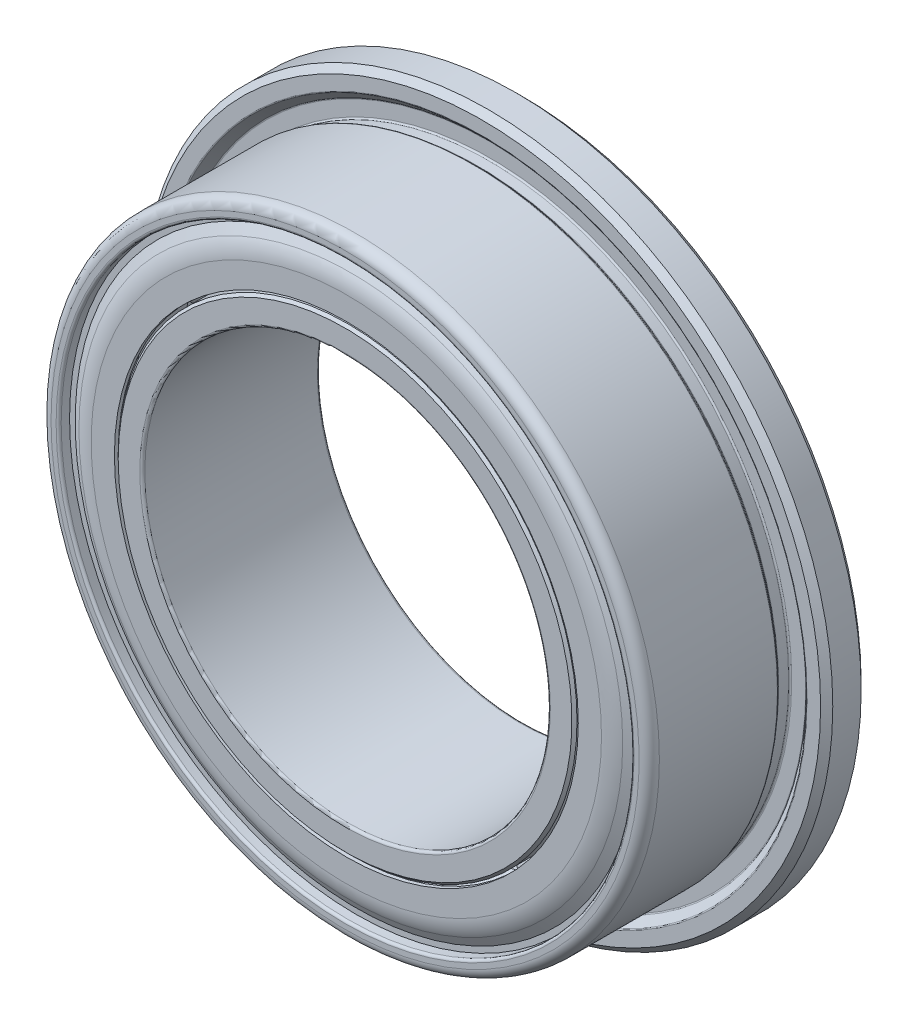
SolidWorks part; units mm, degrees
note: '?' marks a value the reader was unsure of.
ref_plane "Front Plane" through (0, 0, 0) normal (0, 0, 1) x (1, 0, 0)
ref_plane "Top Plane" through (0, 0, 0) normal (0, 1, 0) x (1, 0, 0)
ref_plane "Right Plane" through (0, 0, 0) normal (1, 0, 0) x (0, 0, -1)
sketch "Sketch1" plane through (0, 0, 0) normal (1, 0, 0) x (0, 0, -1)
  line L0 (-1.75, 0) -> (1.75, 0) construction
  line L1 (0, 6) -> (0, -6) construction
  line L2 (1.75, 6) -> (-1.75, 6)
  line L4 (-1.75, 6) -> (-1.75, 5.65)
  line L5 (-1.75, 5.65) -> (-0.645, 5.65)
  line L6 (1.75, 5.65) -> (0.645, 5.65)
  line L7 (1.75, 6) -> (1.75, 5.65)
  line L9 (0, 6) -> (0, 5) construction
  line L10 (0, 5) -> (0, 4) construction
  line L11 (-1.75, -5.65) -> (-1.75, 5.65) construction
  line L12 (0.95, -6.8) -> (1.75, -6.8)
  line L13 (0.95, -6.8) -> (0.95, 6.8)
  line L14 (0.95, 6.8) -> (1.75, 6.8)
  line L15 (1.75, -6.8) -> (1.75, 6.8)
  line L16 (0.95, -6.8) -> (1.75, 6.8) construction
  line L17 (0.95, 6.8) -> (1.75, -6.8) construction
  line L18 (-1.75, -4.525) -> (-1.75, 4.525)
  line L24 (0, -6) -> (-1.75, -6)
  line L25 (0, 4) -> (0, 6) construction
  line L26 (-1.75, 4.525) -> (-1.75, 4)
  line L27 (-1.75, 4) -> (1.75, 4)
  line L28 (1.75, 4) -> (1.75, 4.525)
  line L29 (1.75, 4.525) -> (0.445, 4.525)
  line L30 (-1.75, 4.525) -> (-0.445, 4.525)
  line L31 (-0.645, 5.65) -> (-0.645, 5.425)
  line L32 (-0.645, 5.425) -> (-0.445, 5.425)
  line L33 (0.645, 5.65) -> (0.645, 5.425)
  line L34 (0.645, 5.425) -> (0.445, 5.425)
  arc A3 (-0.445, 4.525) -> (0.445, 4.525) centre (0, 5) ccw
  circle A5 centre (0, 4.9791) radius 0.6
  arc A6 (-0.445, 5.425) -> (0.445, 5.425) centre (0, 4.9791) cw
  point P7 (-1.75, 5.65)
  point P13 (-1.65, 5.65)
  point P14 (0, 4)
  point P15 (1.35, 0)
  point P22 (1.75, 0)
  point P25 (-1.75, 0)
  point P27 (-1.75, 0)
  point P28 (-1.55, 5.65)
  point P29 (-1.45, 5.65)
  point P30 (-1.35, 5.65)
  point P31 (-1.25, 5.65)
  point P32 (-1.15, 5.65)
  point P33 (-1.05, 5.65)
  point P34 (-0.95, 5.65)
  point P37 (-0.85, 5.65)
  point P45 (-0.75, 5.65)
  point P46 (0, 5.6091)
  point P47 (-0.65, 5.65)
  point P50 (0, 4.3491)
  point P51 (0, 4.3791)
  point P52 (0, 5.5791)
  dimension "D3" = 1.2
  dimension "Shaft Dia" = 8
  dimension "Flange Thickness" = 0.8
  dimension "Flange OD" = 13.6
  dimension "D11" = 11.3
  dimension "D10" = 9.05
  dimension "Width" = 3.5
  dimension "OD" = 12
  dimension "D4" = 0.03
  dimension "D5" = 0.2
  dimension "D6" = 0.1
  dimension "D7" = 0.9
  dimension "D1" = 12
sketch "Sketch2" plane through (0, 0, 0) normal (0, 0, 1) x (1, 0, 0)
  line L0 (0, -4.525) -> (0, 4.525) construction
  circle A0 centre (0, 0) radius 4
  dimension "D1" = 8
sketch "Sketch3" plane through (0, 0, 0) normal (1, 0, 0) x (0, 0, -1)
  line L2 (-1.75, 6) -> (-1.75, 5.65) construction
  line L3 (1.75, 6) -> (-1.75, 6) construction
  line L4 (1.75, 6) -> (1.75, 5.65) construction
  line L5 (1.75, 5.65) -> (0.645, 5.65) construction
  line L6 (-1.75, 5.65) -> (-0.645, 5.65) construction
  line L13 (-1.75, 6) -> (-1.75, 5.65)
  line L21 (1.75, 6) -> (-1.75, 6)
  line L22 (1.75, 6) -> (1.75, 5.65)
  line L23 (1.75, 5.65) -> (0.645, 5.65)
  line L24 (-1.75, 5.65) -> (-0.645, 5.65)
  line L25 (1.75, 4) -> (-1.75, 4)
  line L27 (-1.75, 4) -> (-1.75, 4.525)
  line L28 (-1.75, 4.525) -> (-0.445, 4.525)
  line L29 (0.645, 5.65) -> (0.645, 5.425) construction
  line L30 (1.75, 4) -> (1.75, 4.525)
  line L31 (1.75, -6.8) -> (1.75, 6.8) construction
  line L32 (1.75, 4.525) -> (0.445, 4.525)
  line L33 (0.645, 5.425) -> (0.445, 5.425) construction
  line L34 (-0.645, 5.425) -> (-0.445, 5.425) construction
  line L35 (-0.645, 5.65) -> (-0.645, 5.425) construction
  line L36 (0.645, 5.65) -> (0.645, 5.425)
  line L37 (0.645, 5.425) -> (0.445, 5.425)
  line L38 (-0.645, 5.425) -> (-0.445, 5.425)
  line L39 (-0.645, 5.65) -> (-0.645, 5.425)
  arc A4 (0.445, 5.425) -> (-0.445, 5.425) centre (0, 4.9791) ccw construction
  arc A5 (-0.445, 4.525) -> (0.445, 4.525) centre (0, 5) ccw construction
  arc A6 (-0.445, 4.525) -> (0.445, 4.525) centre (0, 5) ccw
  arc A7 (0.445, 5.425) -> (-0.445, 5.425) centre (0, 4.9791) ccw
  point P15 (0, 4)
revolve "Revolve1" add sketch "Sketch3" angle 360 about L0
sketch "Sketch5" plane through (0, 0, 0) normal (1, 0, 0) x (0, 0, -1)
  line L0 (-0.6, 4.9791) -> (0.6, 4.9791)
  line L1 (0, 6) -> (0, -6) construction
  circle A0 centre (0, 4.9791) radius 0.6 construction
  arc A1 (-0.6, 4.9791) -> (0.6, 4.9791) centre (0, 4.9791) cw
revolve "Revolve3" add sketch "Sketch5" angle 360 about L0
ref_axis "Axis1" through (0, 0, -1.75) along (0, 0, 1)?
pattern_circular "CirPattern1" count 12 over 360 about axis through (0, 0, 0) along (0, 0, 1) of bodies 122
sketch "Sketch6" plane through (0, 0, 0) normal (1, 0, 0) x (0, 0, -1)
  line L1 (-1.725, 4.525) -> (-1.725, 5.0332)
  line L2 (-1.6366, 5.3632) -> (-1.5345, 5.54)
  line L4 (-1.5345, 5.54) -> (-1.4479, 5.54) construction
  line L5 (-1.5345, 5.54) -> (-1.5345, 5.65)
  line L6 (-1.5345, 5.65) -> (-1.4479, 5.65)
  line L7 (-1.4479, 5.54) -> (-1.65, 5.1899)
  line L8 (-1.65, 5.1899) -> (-1.65, 4.525)
  line L9 (-1.65, 4.525) -> (-1.725, 4.525)
  line L10 (0, 6) -> (0, -6) construction
  line L11 (-1.4479, 5.65) -> (-1.4479, 5.54)
  line L12 (-1.75, 5.65) -> (-0.645, 5.65) construction
  line L14 (0, 6) -> (0, 5.6091) construction
  arc A0 (-1.725, 5.0332) -> (-1.6366, 5.3632) centre (-1.065, 5.0332) cw
  point P22 (-1.725, 5.21)
  dimension "D8" = 0.66
  dimension "D1" = 30
  dimension "D3" = 0.075
  dimension "D6" = 0.33
  dimension "D5" = 1.125
  dimension "D7" = 0.11
revolve "Revolve4" add sketch "Sketch6" angle 360 about L0
mirror "Mirror1" about plane through (0, 0, 0) normal (0, 0, 1) of bodies 138
sketch "Sketch9" plane through (0, 0, 1.725) normal (0, 0, 1) x (1, 0, 0)
  circle A2 centre (0, 0) radius 4.575
  circle A3 centre (0, 0) radius 4.575
  dimension "D1" = 0.05
extrude "Cut-Extrude1" cut sketch "Sketch9" against normal through all
sketch "Sketch7" plane through (0, 0, 0) normal (1, 0, 0) x (0, 0, -1)
  line L0 (1.75, 0) -> (-1.75, 0) construction
  line L2 (0.95, 6.8) -> (1.75, 6.8)
  line L3 (0.95, 6.8) -> (0.95, 5.65)
  line L4 (0.95, 5.65) -> (1.75, 5.65)
  line L5 (1.75, 6.8) -> (1.75, 5.65)
revolve "Revolve5" add sketch "Sketch7" angle 360 about L0
fillet "Fillet2" radius 0.2 1 edges at (6, 0, 1.75)
fillet "Fillet3" radius 0.05 4 edges at (5.65, 0, -1.75) (5.65, 0, 1.75) (5.65, 0, -0.645) (5.65, 0, 0.645)
fillet "Fillet6" radius 0.05 4 edges at (4.525, 0, -1.75) (4.525, 0, -0.445) (4.525, 0, 0.445) (4.525, 0, 1.75)
sketch "Sketch8" plane through (0, 0, 0) normal (1, 0, 0) x (0, 0, -1)
  line L7 (0.95, 6.8) -> (0.95, 6) construction
  line L8 (0.95, 6.4) -> (1.11, 6.24)
  line L9 (1.11, 6.24) -> (1.11, 5.92)
  line L10 (1.11, 5.92) -> (0.87, 5.92)
  line L11 (0.87, 5.92) -> (0.79, 6)
  line L12 (0.95, 6) -> (-1.55, 6) construction
  line L13 (0.79, 6) -> (0.95, 6)
  line L14 (0.95, 6) -> (0.95, 6.4)
  dimension "D1" = 45
  dimension "D2" = 45
  dimension "D3" = 0.16
  dimension "D5" = 0.08
revolve "Cut-Revolve1" cut sketch "Sketch8" angle 360 about L0
fillet "Fillet5" radius 0.03 5 edges at (6, 0, -0.79) (5.92, 0, -0.87) (5.92, 0, -1.11) (6.24, 0, -1.11) (6.4, 0, -0.95)
chamfer "Chamfer1" distance 0.12 angle 45 2 edges at (-6.8, 0, -0.95) (-6.8, 0, -1.75)
fillet "Fillet7" radius 0.05 2 edges at (4, 0, 1.75) (4, 0, -1.75)
equation "\"Balls@CirPattern1\"=\"D1@Sketch1\""
equation "\"D3@Sketch8\" = \"Flange Thickness@Sketch1\" * .2"
equation "\"D4@Sketch8\" = \"D3@Sketch8\" * .5"
equation "\"D5@Sketch8\" = \"D3@Sketch8\" * .5"
equation "\"D1@Chamfer1\"=\"Flange Thickness@Sketch1\"*.15"
equation "\"D1@Fillet6\"=\"D1@Fillet3\""
equation "\"D4@Sketch1\"=\"D2@Sketch1\""
equation "\"D7@Sketch1\" =  ( \"D11@Sketch1\" - \"D10@Sketch1\" )  * .40"
equation "\"D3@Sketch6\"=\"D4@Sketch6\""
equation "\"D8@Sketch6\"=\"D6@Sketch6\"*2"
